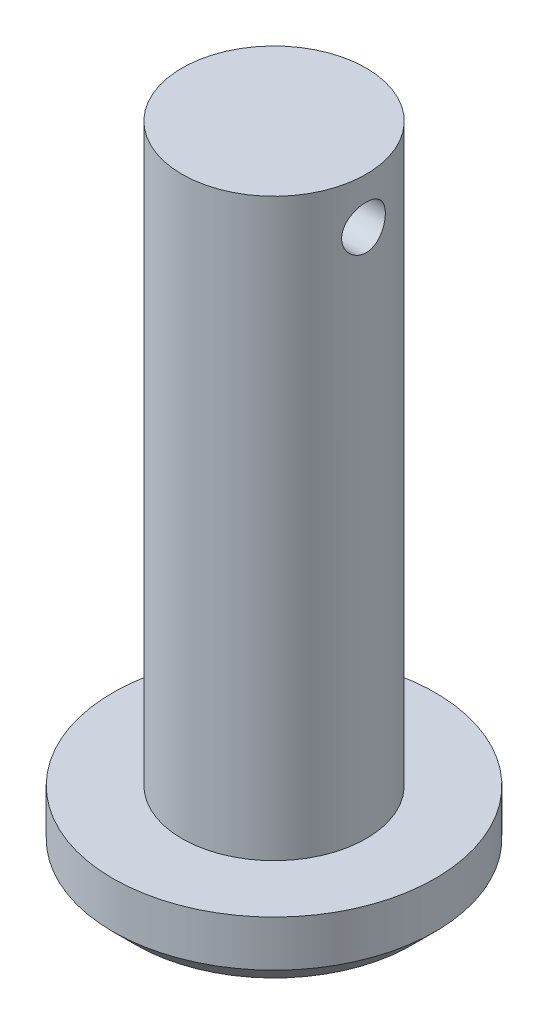
SolidWorks part; units mm, degrees
ref_plane "Front Plane" through (0, 0, 0) normal (0, 0, 1) x (1, 0, 0)
ref_plane "Top Plane" through (0, 0, 0) normal (0, 1, 0) x (1, 0, 0)
ref_plane "Right Plane" through (0, 0, 0) normal (1, 0, 0) x (0, 0, -1)
sketch "Sketch1" plane through (0, 0, 0) normal (0, 1, 0) x (1, 0, 0)
  circle A0 centre (0, 0) radius 7
  circle A1 centre (0, 0) radius 4
  dimension "D1" = 14
  dimension "D2" = 8
extrude "Boss-Extrude1" add sketch "Sketch1" against normal blind 3 contours A0
extrude "Boss-Extrude2" add sketch "Sketch1<3>" along normal blind 25 contours A1
sketch "Sketch1<3>" plane through (0, 0, 0) normal (0, 1, 0) x (1, 0, 0) same geometry as "Sketch1"
ref_plane "Plane1" through (-4, 0, 0) normal (-1, 0, 0) x (0, 0, 1)
sketch "Sketch3" plane through (-4, 0, 0) normal (-1, 0, 0) x (0, 0, 1)
  circle A0 centre (0, 23) radius 0.95
  point P3 (0, 0)
  dimension "D3" = 1.9
  dimension "D1" = 23
extrude "Cut-Extrude1" cut sketch "Sketch3" against normal through all contours A0
chamfer "Chamfer1" distance 1 angle 45 1 edges at (0, -3, 7)
